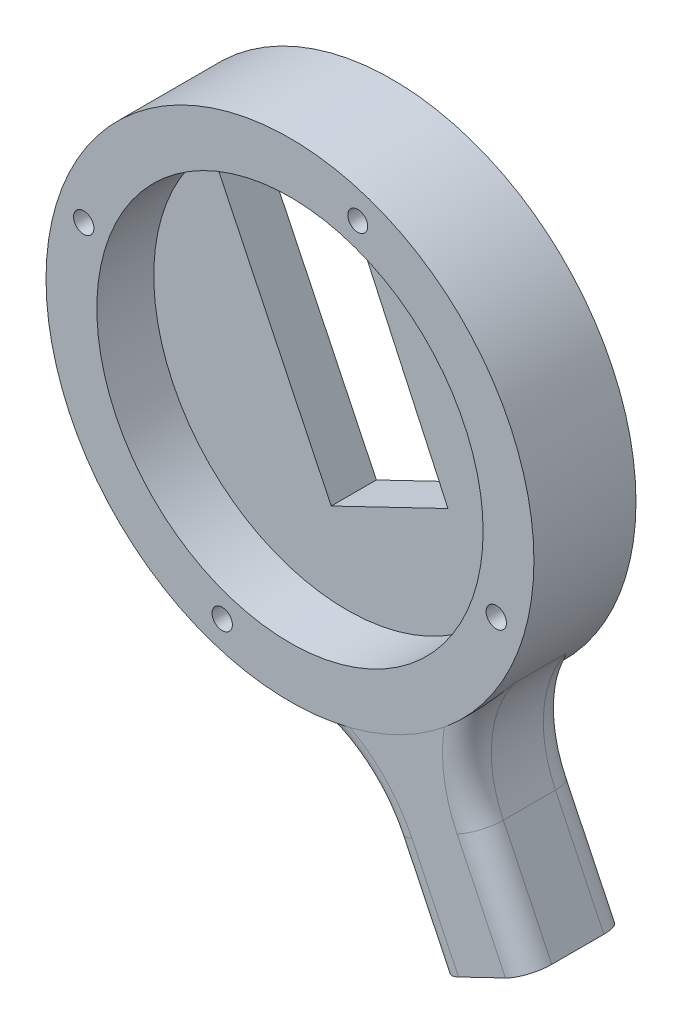
SolidWorks part; units mm, degrees
ref_plane "Front Plane" through (0, 0, 0) normal (0, 0, 1) x (1, 0, 0)
ref_plane "Top Plane" through (0, 0, 0) normal (0, 1, 0) x (1, 0, 0)
ref_plane "Right Plane" through (0, 0, 0) normal (1, 0, 0) x (0, 0, -1)
sketch "Sketch1" plane through (0, 0, 0) normal (0, 0, 1) x (1, 0, 0)
  circle A0 centre (0, 0) radius 60
  dimension "D1" = 120
extrude "Boss-Extrude1" add sketch "Sketch1" along normal blind 25.1
sketch "Sketch2" plane through (0, 0, 25.1) normal (0, 0, 1) x (1, 0, 0)
  circle A0 centre (-16.6647, -50.7331) radius 2.495
  circle A1 centre (-50.7331, 16.6647) radius 2.5
  circle A2 centre (16.6647, 50.7331) radius 2.4444
  circle A3 centre (50.7331, -16.6647) radius 2.5
sketch "Sketch3" plane through (0, 0, 25.1) normal (0, 0, 1) x (1, 0, 0)
  circle A0 centre (0, 0) radius 47.5
  dimension "D1" = 95
extrude "Cut-Extrude2" cut sketch "Sketch3" against normal blind 14
extrude "Cut-Extrude5" cut sketch "Sketch2" against normal through all both and the other way through all
sketch "Sketch6" plane through (0, 0, 0) normal (0, 0, -1) x (-1, 0, 0)
  circle A0 centre (11.9735, 47.2126) radius 3
  circle A1 centre (27.3813, 40.0293) radius 3
  circle A2 centre (-19.7177, -20.7629) radius 3
  circle A3 centre (-4.3099, -27.9462) radius 3
  dimension "D1" = 6
  dimension "D2" = 6
  dimension "D3" = 6
  dimension "D4" = 6
extrude "Cut-Extrude6" cut sketch "Sketch6" against normal blind 6
sketch "Sketch7" plane through (0, 0, 11.1) normal (0, 0, 1) x (1, 0, 0)
  line L0 (-32.7224, 32.7144) -> (-3.8455, -27.2733)
  line L1 (-3.8455, -27.2733) -> (24.8593, -13.4553)
  line L2 (24.8593, -13.4553) -> (-3.0425, 47.0016)
  line L3 (-3.0425, 47.0016) -> (-32.7224, 32.7144)
  circle A0 centre (0, 0) radius 47.1 construction
extrude "Cut-Extrude7" cut sketch "Sketch7" against normal through all both and the other way through all
ref_plane "Plane1" through (33.1075, -68.7763, 0) normal (0.4337, -0.901, 0) x (-0.901, -0.4337, 0)
sketch "Sketch8" plane through (33.1075, -68.7763, 0) normal (0.4337, -0.901, 0) x (-0.901, -0.4337, 0)
  line L1 (-13.3812, -0.0782) -> (11.4188, -0.0782)
  line L2 (-13.3812, -0.0782) -> (-13.3812, -24.8782)
  line L3 (-13.3812, -24.8782) -> (11.4188, -24.8782)
  line L4 (11.4188, -0.0782) -> (11.4188, -24.8782)
  line L5 (-13.3812, -0.0782) -> (11.4188, -24.8782) construction
  line L6 (-13.3812, -24.8782) -> (11.4188, -0.0782) construction
  point P0 (-0.9812, -12.4782)
  dimension "D1" = 24.8
  dimension "D2" = 24.8
extrude "Boss-Extrude2" add sketch "Sketch8" along normal blind 30 and the other way blind 23
fillet "Fillet1" radius 30 2 edges at (15.2601, -58.027, 12.4782) (37.426, -46.8967, 12.4782)
sketch "Sketch9" plane through (46.1197, -95.8074, 0) normal (0.4337, -0.901, 0) x (0.901, 0.4337, 0)
  circle A0 centre (0.9812, 12.4782) radius 6.1
  dimension "D1" = 12.2
extrude "Cut-Extrude8" cut sketch "Sketch9" against normal blind 40
fillet "Fillet2" radius 6 8 edges at (13.6743, -64.7991, 0.0782) (43.3997, -49.6795, 0.0782) (43.3997, -49.6795, 24.8782) (13.6743, -64.7991, 24.8782) (30.0997, -88.8543, 0.0782) (52.2181, -77.6253, 0.0782) (52.2181, -77.6253, 24.8782) (30.0997, -88.8543, 24.8782)
